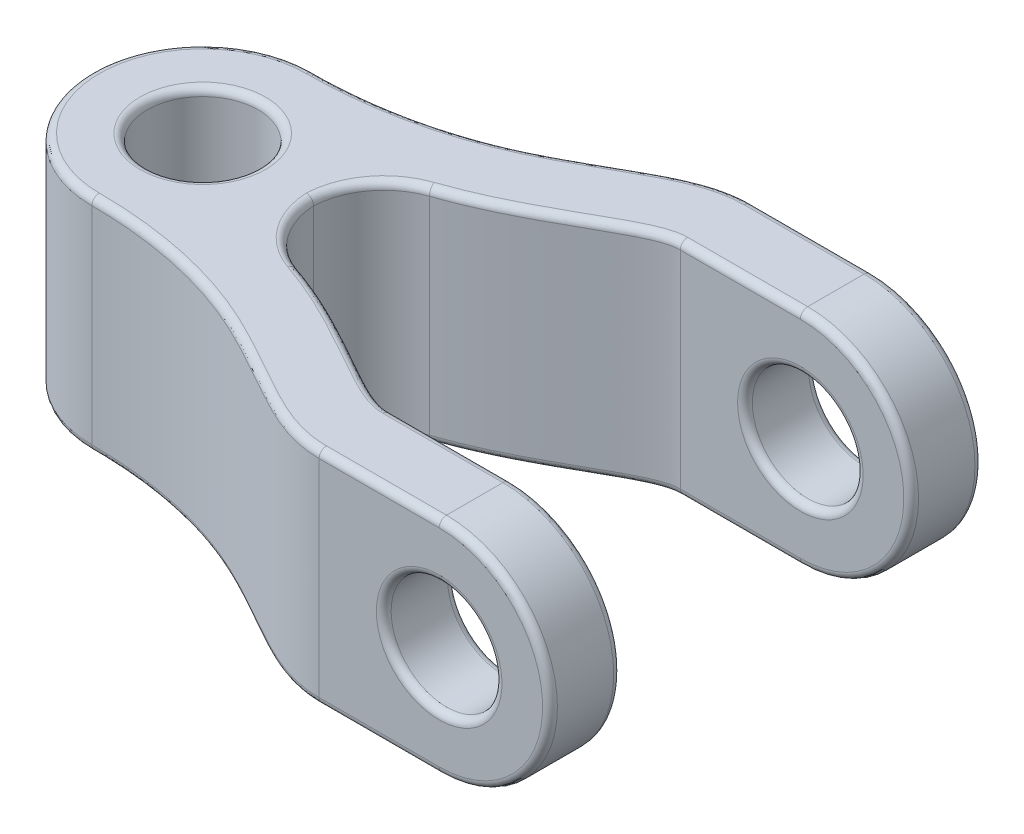
SolidWorks part; units mm, degrees
ref_plane "Alzado" through (0, 0, 0) normal (0, 0, 1) x (1, 0, 0)
ref_plane "Planta" through (0, 0, 0) normal (0, 1, 0) x (1, 0, 0)
ref_plane "Vista lateral" through (0, 0, 0) normal (1, 0, 0) x (0, 0, -1)
sketch "Croquis1" plane through (0, 0, 0) normal (0, 1, 0) x (1, 0, 0)
  line L0 (122.5, 58.51) -> (90, 58.51)
  line L1 (15, 0) -> (61.8814, 0) construction
  line L2 (122.5, -58.51) -> (90, -58.51)
  line L3 (122.5, 39.26) -> (90, 39.26)
  line L4 (122.5, -39.26) -> (90, -39.26)
  line L5 (122.5, 58.51) -> (122.5, 39.26)
  line L6 (122.5, -58.51) -> (122.5, -39.26)
  arc A1 (0, 30) -> (0, -30) centre (0, 0) ccw
  arc A2 (26.8356, -13.4109) -> (26.8356, 13.4109) centre (0, 0) ccw
  circle A3 centre (0, 0) radius 15
  spline S0 degree 3 poles (90, 58.51) (81.4772, 58.51) (66.1677, 50.5751) (39.0281, 34.5081) (14.9373, 30) (0, 30) knots 0 0 0 0 0.25787 0.52906 1 1 1 1
  spline S1 degree 3 poles (90, -58.51) (81.4772, -58.51) (66.1677, -50.5751) (39.0281, -34.5081) (14.9373, -30) (0, -30) knots 0 0 0 0 0.25787 0.52906 1 1 1 1
  spline S2 degree 1 poles (90, 39.26) (0, 10.75) knots 0 0 1 1 construction
  spline S3 degree 3 poles (90, 39.26) (89.662, 39.26) (89.0137, 39.2248) (87.5075, 38.9938) (85.1449, 38.3134) (81.4031, 36.6703) (77.6047, 34.6372) (74.2012, 32.744) (70.7601, 30.8163) (66.2879, 28.3149) (60.605, 25.2721) (54.5393, 22.29) (47.9892, 19.5016) (41.3376, 17.1347) (34.8462, 15.2249) (29.4241, 13.9273) (22.5423, 12.5437) (13.0096, 11.1744) (4.634, 10.75) (0, 10.75) knots 0 0 0 0 0.03125 0.0625 0.125 0.1875 0.25 0.28125 0.3125 0.375 0.4375 0.5 0.5625 0.625 0.6875 0.742384 0.773634 0.875 1 1 1 1 only from (90, 39.26) to (26.8356, 13.4109)
  spline S4 degree 1 poles (90, -39.26) (0, -10.75) knots 0 0 1 1 construction
  spline S5 degree 3 poles (90, -39.26) (89.662, -39.26) (89.0137, -39.2248) (87.5075, -38.9938) (85.1449, -38.3134) (81.4031, -36.6703) (77.6047, -34.6372) (74.2012, -32.744) (70.7601, -30.8163) (66.2879, -28.3149) (60.605, -25.2721) (54.5393, -22.29) (47.9892, -19.5016) (41.3376, -17.1347) (34.8462, -15.2249) (29.4241, -13.9273) (22.5423, -12.5437) (13.0096, -11.1744) (4.634, -10.75) (0, -10.75) knots 0 0 0 0 0.03125 0.0625 0.125 0.1875 0.25 0.28125 0.3125 0.375 0.4375 0.5 0.5625 0.625 0.6875 0.742384 0.773634 0.875 1 1 1 1 only from (90, -39.26) to (26.8356, -13.4109)
  point P4 (122.5, 58.51)
  point P15 (122.5, -58.51)
  dimension "D1" = 30
  dimension "D2" = 60
  dimension "D3" = 58.51
  dimension "D4" = 122.5
  dimension "D5" = 32.5
  dimension "D6" = 19.25
  dimension "D7" = 19.25
extrude "Saliente-Extruir1" add sketch "Croquis1" along normal blind 60
sketch "Croquis2" plane through (0, 0, 58.51) normal (0, 0, 1) x (1, 0, 0)
  line L0 (122.5, 60) -> (122.5, 0) construction
  circle A0 centre (122.5, 30) radius 30
extrude "Saliente-Extruir2" add sketch "Croquis2" against normal up to surface (19.25 mm away) up to face at (106.25, 30, 39.26)
sketch "Croquis3" plane through (0, 0, -58.51) normal (0, 0, -1) x (-1, 0, 0)
  line L0 (-122.5, 60) -> (-122.5, 0) construction
  circle A1 centre (-122.5, 30) radius 30
extrude "Saliente-Extruir3" add sketch "Croquis3" against normal up to surface (19.25 mm away) up to face at (106.25, 30, -39.26)
sketch "Croquis4" plane through (0, 0, 58.51) normal (0, 0, 1) x (1, 0, 0)
  circle A0 centre (122.5, 30) radius 15
  dimension "D1" = 30
extrude "Cortar-Extruir1" cut sketch "Croquis4" against normal through all and the other way through all
fillet "Redondeo1" radius 20 2 edges at (26.8356, 30, 13.4109) (26.8356, 30, -13.4109)
fillet "Redondeo2" radius 2 32 edges at (152.5, 30, -58.51) (106.25, 0, -58.51) (-30, 0, 0) (106.25, 0, 58.51) (152.5, 30, 58.51) (33.9968, 0, -11.0192) (106.25, 0, -39.26) (152.5, 30, -39.26) (33.9968, 0, 11.0192) (106.25, 0, 39.26) (152.5, 30, 39.26) (107.5, 30, 58.51) (137.5, 30, 39.26) (107.5, 30, -39.26) (137.5, 30, -58.51) (0, 60, 15) (106.25, 60, 39.26) (106.25, 60, 58.51) (-30, 60, 0) (106.25, 60, -58.51) (106.25, 60, -39.26) (33.9968, 60, -11.0192) (33.9968, 60, 11.0192) (0, 0, 15)
